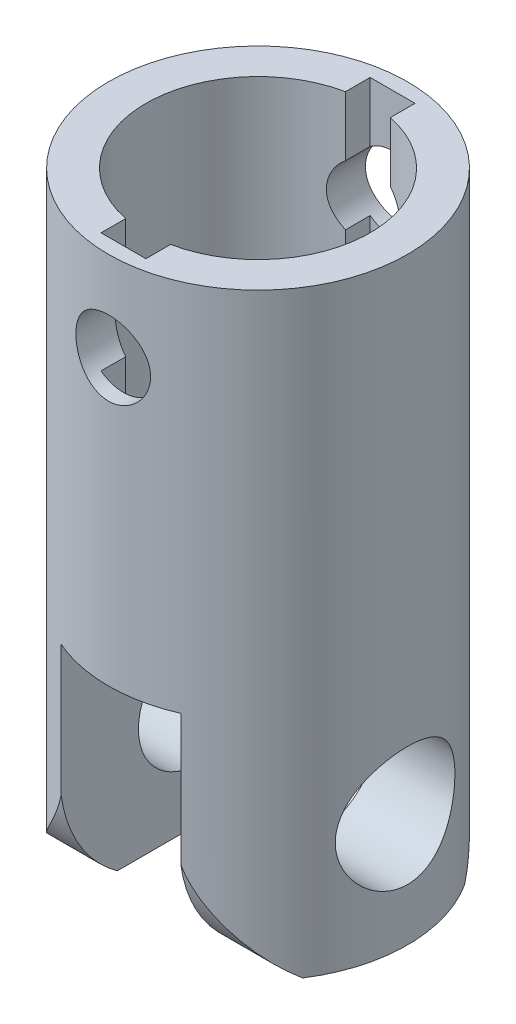
SolidWorks part; units mm, degrees
ref_plane "Front Plane" through (0, 0, 0) normal (0, 0, 1) x (1, 0, 0)
ref_plane "Top Plane" through (0, 0, 0) normal (0, 1, 0) x (1, 0, 0)
ref_plane "Right Plane" through (0, 0, 0) normal (1, 0, 0) x (0, 0, -1)
sketch "Sketch1" plane through (0, 0, 0) normal (0, 1, 0) x (1, 0, 0)
  circle A1 centre (0, 0) radius 10
  dimension "D2" = 20
extrude "Boss-Extrude1" add sketch "Sketch1" along normal blind 25
sketch "Sketch3" plane through (0, 0, 0) normal (0, 1, 0) x (1, 0, 0)
  line L6 (-4, 9.1652) -> (-4, -9.1652)
  line L8 (4, 9.1652) -> (4, -9.1652)
  line L9 (-4, 9.1652) -> (4, -9.1652) construction
  line L10 (-4, -9.1652) -> (4, 9.1652) construction
  circle A3 centre (0, 0) radius 10 construction
  arc A4 (4, -9.1652) -> (4, 9.1652) centre (0, 0) ccw
  arc A5 (-4, 9.1652) -> (-4, -9.1652) centre (0, 0) ccw
  point P0 (0, 0)
  dimension "D1" = 8
extrude "Boss-Extrude2" add sketch "Sketch3" against normal blind 15
sketch "Sketch4" plane through (0, 0, 0) normal (1, 0, 0) x (0, 0, -1)
  line L1 (9.25, -7.5) -> (14.8444, -7.5)
  line L2 (14.8444, -7.5) -> (14.8444, -20.1573)
  line L3 (14.8444, -20.1573) -> (-15.4028, -20.1573)
  line L4 (-15.4028, -20.1573) -> (-15.4028, -7.5)
  line L5 (-15.4028, -7.5) -> (-9.25, -7.5)
  line L6 (-9.1652, -15) -> (9.1652, -15) construction
  circle A0 centre (0, -7.5) radius 4
  arc A1 (-9.25, -7.5) -> (9.25, -7.5) centre (0, -7.5) ccw
  dimension "D2" = 9.25
  dimension "D3" = 8
  dimension "D1" = 7.5
extrude "Cut-Extrude2" cut sketch "Sketch4" against normal blind 20 and the other way blind 20
sketch "Sketch5" plane through (0, 25, 0) normal (0, 1, 0) x (1, 0, 0)
  circle A0 centre (0, 0) radius 7.5
  dimension "D1" = 15
extrude "Cut-Extrude3" cut sketch "Sketch5" against normal blind 20
sketch "Sketch6" plane through (0, 0, 0) normal (0, 0, 1) x (1, 0, 0)
  line L0 (10, 25) -> (-10, 25) construction
  circle A0 centre (0, 19) radius 2.5
  dimension "D2" = 5
  dimension "D1" = 6
extrude "Cut-Extrude4" cut sketch "Sketch6" against normal blind 10 and the other way blind 10
sketch "Sketch7" plane through (0, 25, 0) normal (0, 1, 0) x (1, 0, 0)
  line L1 (-1.5, -9) -> (1.5, -9)
  line L2 (-1.5, -9) -> (-1.5, 9)
  line L3 (-1.5, 9) -> (1.5, 9)
  line L4 (1.5, -9) -> (1.5, 9)
  line L5 (-1.5, -9) -> (1.5, 9) construction
  line L6 (-1.5, 9) -> (1.5, -9) construction
  point P0 (0, 0)
  dimension "D1" = 3
  dimension "D2" = 18
extrude "Cut-Extrude5" cut sketch "Sketch7" against normal blind 20
